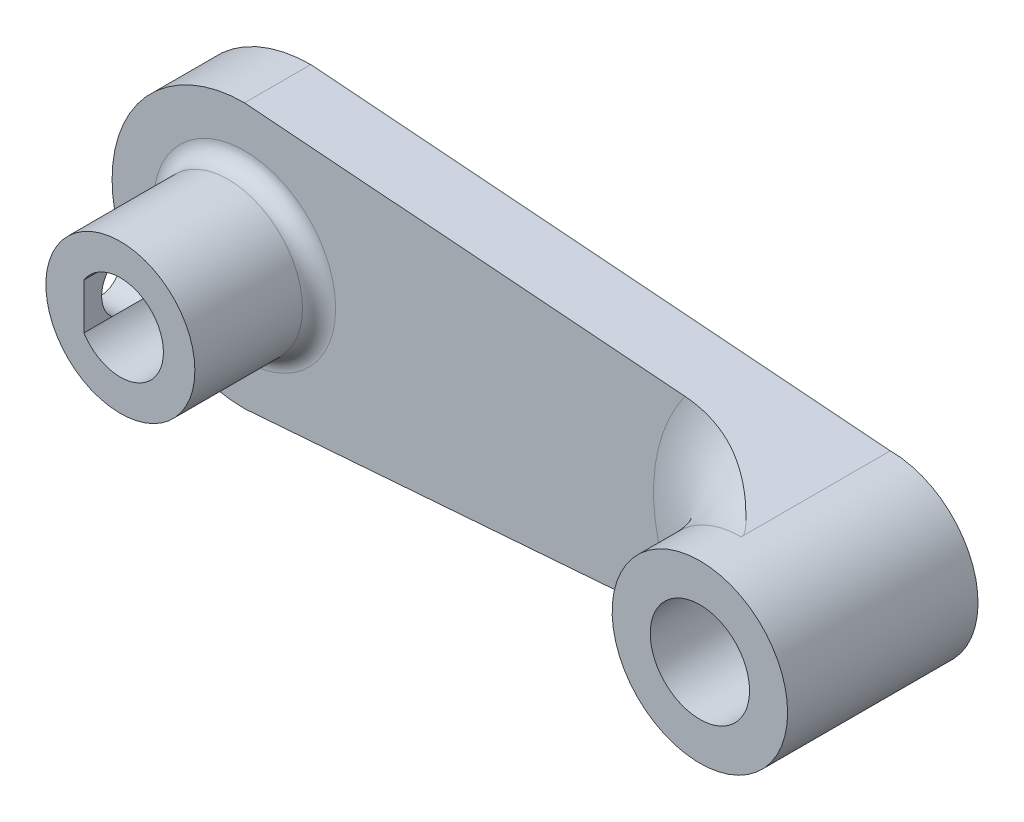
SolidWorks part; units mm, degrees
ref_plane "Front Plane" through (0, 0, 0) normal (0, 0, 1) x (1, 0, 0)
ref_plane "Top Plane" through (0, 0, 0) normal (0, 1, 0) x (1, 0, 0)
ref_plane "Right Plane" through (0, 0, 0) normal (1, 0, 0) x (0, 0, -1)
sketch "Sketch1" plane through (0, 0, 0) normal (0, 0, 1) x (1, 0, 0)
  line L0 (-2.2004, 1.385) -> (-2.2004, -1.385)
  line L1 (0, 0) -> (35, 0) construction
  line L2 (0, 8) -> (35, 5.2993)
  line L3 (0, -8) -> (35.4054, -5.2838)
  arc A0 (-2.2004, -1.385) -> (-2.2004, 1.385) centre (0, 0) ccw
  circle A1 centre (35, 0) radius 3.2
  arc A2 (0, 8) -> (0, -8) centre (0, 0) ccw
  arc A3 (35.4054, -5.2838) -> (35, 5.2993) centre (35, 0) ccw
  dimension "D1" = 5.2
  dimension "D3" = 6.4
  dimension "D5" = 8
  dimension "D2" = 2.77
  dimension "D4" = 35
extrude "Boss-Extrude1" add sketch "Sketch1" along normal blind 4
sketch "Sketch2" plane through (0, 0, 4) normal (0, 0, 1) x (1, 0, 0)
  line L0 (-2.2004, 1.385) -> (-2.2004, -1.385)
  arc A0 (-2.2004, 1.385) -> (-2.2004, -1.385) centre (0, 0) cw
  circle A2 centre (0, 0) radius 4.5
  arc A3 (-2.2004, -1.385) -> (-2.2004, 1.385) centre (0, 0) ccw construction
  point P6 (0, 0)
  dimension "D1" = 9
extrude "Boss-Extrude2" add sketch "Sketch2" along normal blind 7.5
fillet "Fillet2" radius 1 1 edges at (4.5, 0, 4)
sketch "Sketch3" plane through (0, 0, 4) normal (0, 0, 1) x (1, 0, 0)
  circle A0 centre (35, 0) radius 3
  circle A1 centre (35, 0) radius 5.2993
  arc A3 (35.4054, -5.2838) -> (35, 5.2993) centre (35, 0) ccw construction
  dimension "D1" = 6
extrude "Boss-Extrude3" add sketch "Sketch3" along normal up to surface (7.5 mm away) up to face at (4.5, 0, 11.5)
sketch "Sketch4" plane through (-2.2004, 0, 0) normal (1, 0, 0) x (0, 0, -1)
  line L0 (-11.5, 0) -> (-5.6631, 0) construction
  line L1 (-11.5, 1.385) -> (-11.5, -1.385) construction
  line L2 (-5.6631, 0) -> (4.0309, 1.942) construction
  circle A0 centre (-8.5816, 0) radius 1.85
  dimension "D1" = 3.7
extrude "Cut-Extrude1" cut sketch "Sketch4" against normal blind 6
fillet "Fillet3" radius 5 1 edges at (29.7046, -0.2028, 4)
